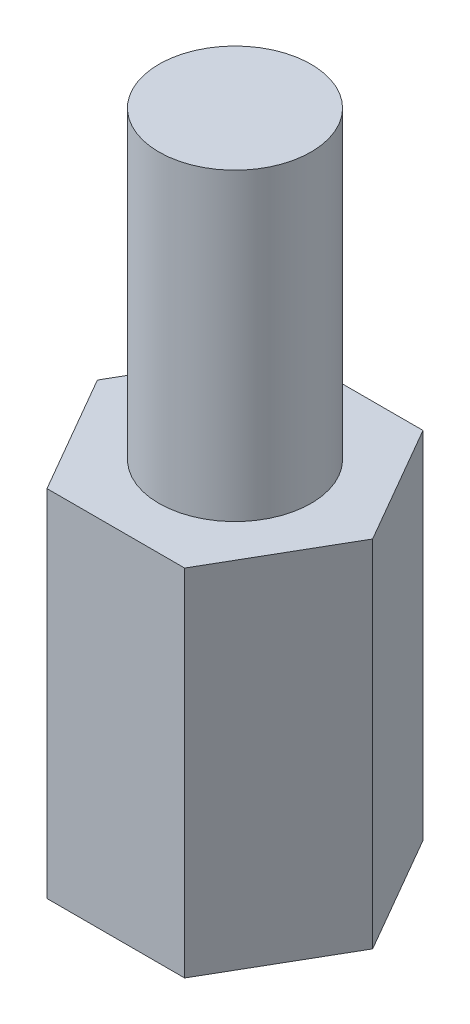
SolidWorks part; units mm, degrees
material "黄铜"
ref_plane "前视基准面" through (0, 0, 0) normal (0, 0, 1) x (1, 0, 0)
ref_plane "上视基准面" through (0, 0, 0) normal (0, 1, 0) x (1, 0, 0)
ref_plane "右视基准面" through (0, 0, 0) normal (1, 0, 0) x (0, 0, -1)
sketch "草图1" plane through (0, 0, 0) normal (0, 1, 0) x (1, 0, 0)
  line L1 (2.7135, 0) -> (1.3568, 2.35)
  line L2 (1.3568, 2.35) -> (-1.3568, 2.35)
  line L3 (-1.3568, 2.35) -> (-2.7135, 0)
  line L4 (-2.7135, 0) -> (-1.3568, -2.35)
  line L5 (-1.3568, -2.35) -> (1.3568, -2.35)
  line L6 (1.3568, -2.35) -> (2.7135, 0)
  circle A0 centre (0, 0) radius 2.35 construction
  circle A1 centre (0, 0) radius 1.5
  dimension "D1" = 3
  dimension "D2" = 4.7
extrude "凸台-拉伸1" add sketch "草图1" against normal blind 7
cosmetic thread "装饰螺纹线2" parameters "D2"=6
extrude "凸台-拉伸2" add sketch "草图1<4>" along normal blind 6 and the other way blind 1 contours A1 region at (0, 0, 0)
sketch "草图1<4>" plane through (0, 0, 0) normal (0, 1, 0) x (1, 0, 0) same geometry as "草图1"
cosmetic thread "装饰螺纹线1" parameters "D2"=1
